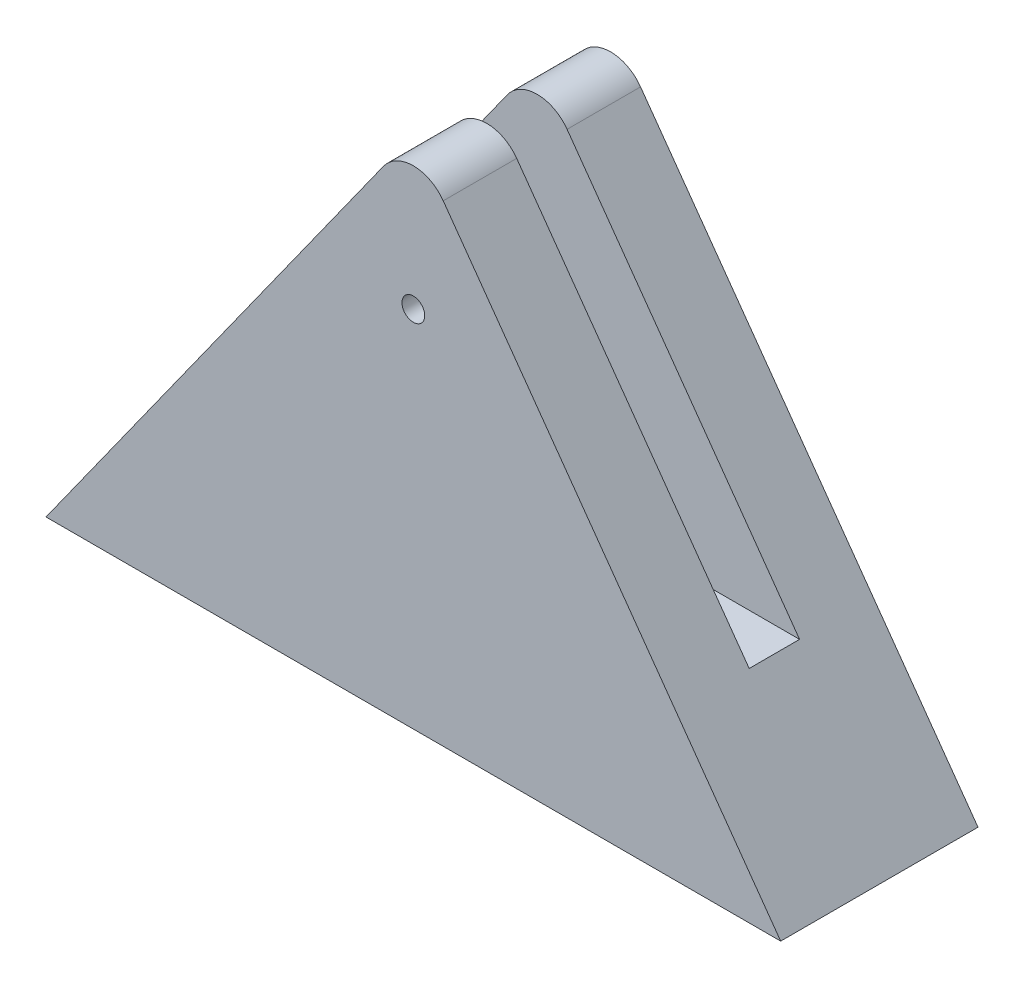
SolidWorks part; units mm, degrees
ref_plane "Front Plane" through (0, 0, 0) normal (0, 0, 1) x (1, 0, 0)
ref_plane "Top Plane" through (0, 0, 0) normal (0, 1, 0) x (1, 0, 0)
ref_plane "Right Plane" through (0, 0, 0) normal (1, 0, 0) x (0, 0, -1)
sketch "Sketch1" plane through (0, 0, 0) normal (0, 0, 1) x (1, 0, 0)
  line L0 (-47.8529, -42.6801) -> (2.1471, 27.3199)
  line L1 (2.1471, 27.3199) -> (52.1471, -42.6801)
  line L2 (52.1471, -42.6801) -> (-47.8529, -42.6801)
  dimension "D1" = 70
  dimension "D2" = 100
extrude "Boss-Extrude1" add sketch "Sketch1" along normal blind 26.858
ref_plane "Plane1" through (52.1471, 0, 0) normal (-1, 0, 0) x (0, 0, 1)
sketch "Sketch2" plane through (52.1471, 0, 0) normal (-1, 0, 0) x (0, 0, 1)
  line L0 (26.858, 27.3199) -> (0, 27.3199) construction
  line L1 (10, 27.3199) -> (16.858, 27.3199)
  line L2 (10, 27.3199) -> (10, -22.6801)
  line L3 (10, -22.6801) -> (16.858, -22.6801)
  line L4 (16.858, 27.3199) -> (16.858, -22.6801)
  line L5 (13.429, 27.3199) -> (13.429, -42.6801) construction
  line L6 (26.858, -42.6801) -> (0, -42.6801) construction
  dimension "D1" = 6.858
  dimension "D2" = 20
extrude "Cut-Extrude1" cut sketch "Sketch2" along normal up to surface (50 mm away) up to face at (-22.8529, -7.6801, 13.429)
sketch "Sketch3" plane through (0, 0, 26.858) normal (0, 0, 1) x (1, 0, 0)
  line L0 (2.1471, -42.6801) -> (2.1471, 34.9099) construction
  line L1 (-47.8529, -42.6801) -> (52.1471, -42.6801) construction
  circle A0 centre (2.1471, 6.8199) radius 1.55
  dimension "D1" = 3.1
  dimension "D2" = 49.5
extrude "Cut-Extrude2" cut sketch "Sketch3" against normal up to surface (26.858 mm away) up to face at (2.1471, -19.3468, 0)
fillet "Fillet1" radius 5 2 edges at (2.1471, 27.3199, 5) (2.1471, 27.3199, 21.858)
sketch "Sketch4" plane through (0, -22.6801, 0) normal (0, 1, 0) x (1, 0, 0)
  line L0 (-33.5672, -13.429) -> (37.8614, -13.429) construction
  line L1 (-33.5672, -16.858) -> (-33.5672, -10) construction
  line L2 (37.8614, -16.858) -> (37.8614, -10) construction
  line L3 (2.1471, -26.858) -> (2.1471, 0) construction
  line L4 (-1.9216, -26.858) -> (6.2157, -26.858) construction
  line L5 (6.2157, 0) -> (-1.9216, 0) construction
  circle A0 centre (-12.8529, -13.429) radius 1.55
  circle A1 centre (17.1471, -13.429) radius 1.55
  dimension "D1" = 3.1
  dimension "D2" = 30
extrude "Cut-Extrude3" cut sketch "Sketch4" against normal through all
